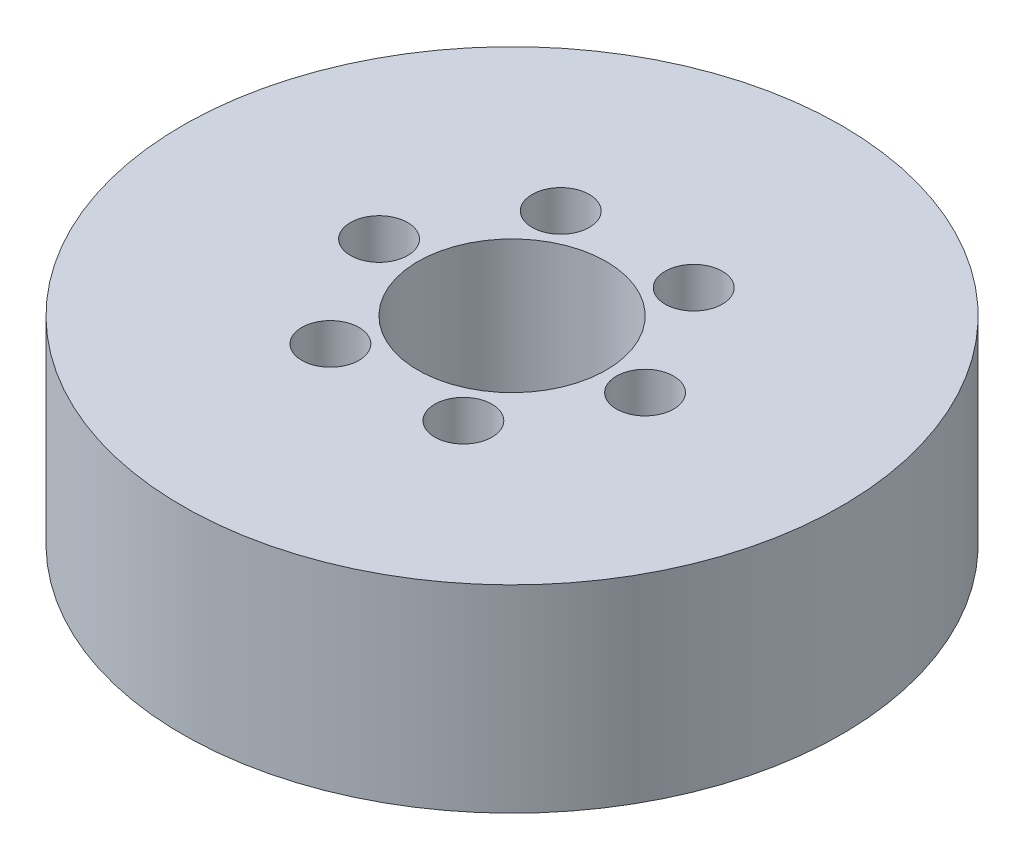
SolidWorks part; units mm, degrees
ref_plane "Front Plane" through (0, 0, 0) normal (0, 0, 1) x (1, 0, 0)
ref_plane "Top Plane" through (0, 0, 0) normal (0, 1, 0) x (1, 0, 0)
ref_plane "Right Plane" through (0, 0, 0) normal (1, 0, 0) x (0, 0, -1)
sketch "Sketch1" plane through (0, 0, 0) normal (0, 1, 0) x (1, 0, 0)
  circle A0 centre (0, 0) radius 35
  dimension "FLANGE_OD" = 70
extrude "Boss-Extrude1" add sketch "Sketch1" along normal blind 21
sketch "Sketch2" plane through (0, 0, 0) normal (0, 1, 0) x (1, 0, 0)
  circle A0 centre (0, 0) radius 10
  dimension "BORE_D" = 20
extrude "Cut-Extrude1" cut sketch "Sketch2" along normal through all
sketch "Sketch3" plane through (0, 21, 0) normal (0, 1, 0) x (1, 0, 0)
  circle A0 centre (0, 0) radius 14.1235 construction
  circle A1 centre (-14.1235, 0) radius 3.0376
  dimension "BOLT_D" = 6.0752
  dimension "BOLT_PCD" = 28.2469
extrude "Cut-Extrude2" cut sketch "Sketch3" against normal blind 18.8118
pattern_circular "CirPattern1" count 6 over 360 about axis through (0, 0, 0) along (0, 1, 0) of "Cut-Extrude2"
